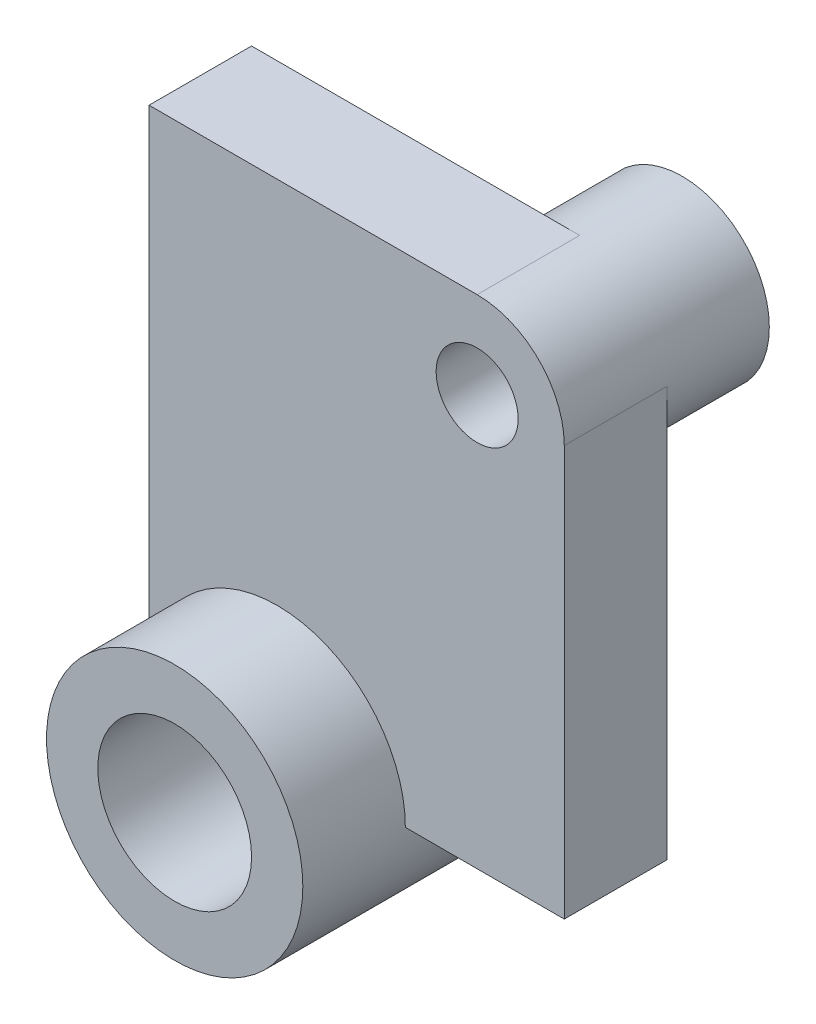
SolidWorks part; units mm, degrees
ref_plane "Спереди" through (0, 0, 0) normal (0, 0, 1) x (1, 0, 0)
ref_plane "Сверху" through (0, 0, 0) normal (0, 1, 0) x (1, 0, 0)
ref_plane "Справа" through (0, 0, 0) normal (1, 0, 0) x (0, 0, -1)
sketch "Эскиз1" plane through (0, 0, 0) normal (0, 0, 1) x (1, 0, 0)
  line L0 (0, 0) -> (0, -40) construction
  line L1 (13, -40) -> (13, -15)
  line L2 (13, -15) -> (8.1885, 2.28)
  line L3 (-13, -40) -> (-32, -40)
  line L4 (-32, -40) -> (-32, -15)
  line L5 (-32, -15) -> (-5.3529, 6.6028)
  line L6 (-13, -40) -> (-8.5, -40)
  line L7 (13, -40) -> (8.5, -40)
  circle A0 centre (0, 0) radius 5.5
  circle A1 centre (0, -40) radius 13
  circle A2 centre (0, 0) radius 8.5
  circle A3 centre (0, -40) radius 8.5
  circle A4 centre (0, 0) radius 4
  dimension "D1" = 11
  dimension "D2" = 26
  dimension "D7" = 17
  dimension "D8" = 8
  dimension "D3" = 40
  dimension "D5" = 45
  dimension "D6" = 25
  dimension "D4" = 3
extrude "Бобышка-Вытянуть1" add sketch "Эскиз1" along normal blind 10 contours A2 L0 A1 L1 L2 | L0 A2 L5 L4 L3 A1 | A1 A3 | A0 A2 | A0 | L0 A1 L6 A3 | A1 L0 A3 L7 | A3 region at (-3.7791, 3.7791, 0) region at (-7.7851, -2.7593, 0) region at (6.9511, -18.2389, 0) region at (-16.6766, -20.8491, 0) region at (6.9436, -33.0564, 0) region at (-6.9436, -33.0564, 0) region at (5.8404, -34.1596, 0) region at (0, -52.7093, 0)
sketch "Эскиз2" plane through (0, 0, 10) normal (0, 0, 1) x (1, 0, 0)
  line L0 (-13, -40) -> (13, -40)
  arc A0 (-13, -40) -> (13, -40) centre (0, -40) ccw construction
  arc A1 (-13, -40) -> (13, -40) centre (0, -40) ccw
extrude "Вырез-Вытянуть1" cut sketch "Эскиз2" against normal through all
sketch "Эскиз3" plane through (0, 0, 10) normal (0, 0, 1) x (1, 0, 0)
  line L0 (13, -40) -> (-32, -40) construction
  line L1 (-32, -40) -> (-32, -15) construction
  circle A0 centre (-19.5, -40) radius 12.5
  dimension "D1" = 25
extrude "Бобышка-Вытянуть2" add sketch "Эскиз3" against normal up to surface (10 mm away) contours A0 up to face at (-5.6662, -16.2435, 0)
sketch "Эскиз4" plane through (0, 0, 10) normal (0, 0, 1) x (1, 0, 0)
  circle A0 centre (-19.5, -40) radius 7.5
  dimension "D1" = 15
extrude "Вырез-Вытянуть2" cut sketch "Эскиз4" against normal up to next
sketch "Эскиз5" plane through (0, 0, 10) normal (0, 0, 1) x (1, 0, 0)
  circle A0 centre (-19.5, -40) radius 7.5
  circle A1 centre (-19.5, -40) radius 12.5
  circle A3 centre (-19.5, -40) radius 7.5 construction
extrude "Бобышка-Вытянуть3" add sketch "Эскиз5" along normal blind 10
sketch "Эскиз6" plane through (0, 0, 0) normal (0, 0, -1) x (-1, 0, 0)
  circle A0 centre (0, 0) radius 4 construction
  circle A1 centre (0, 0) radius 4
  circle A2 centre (0, 0) radius 8.5
extrude "Бобышка-Вытянуть4" add sketch "Эскиз6" along normal blind 10
sketch "Эскиз7" plane through (0, 0, 10) normal (0, 0, 1) x (1, 0, 0)
  line L0 (-32, -15) -> (-32, 8.5)
  line L1 (-32, 8.5) -> (13, 8.5)
  line L2 (13, 8.5) -> (13, -15)
  line L3 (13, -40) -> (13, -15) construction
  line L4 (-32, -15) -> (-5.3529, 6.6028) construction
  line L5 (13, -15) -> (8.1885, 2.28) construction
  line L6 (-32, -15) -> (-5.3529, 6.6028)
  line L7 (13, -15) -> (8.1885, 2.28)
  arc A0 (8.1885, 2.28) -> (-5.3529, 6.6028) centre (0, 0) ccw construction
  arc A1 (8.1885, 2.28) -> (-5.3529, 6.6028) centre (0, 0) ccw
  line M4 (13, -15) -> (8.1885, 2.28)
  arc M5 (8.1885, 2.28) -> (-5.3529, 6.6028) centre (0, 0) ccw
  line M6 (-5.3529, 6.6028) -> (-32, -15)
extrude "Бобышка-Вытянуть5" add sketch "Эскиз7" against normal up to surface (10 mm away) contours L1 L0 M6 M5 | L2 L1 M5 M4 region at (10.3149, 1.2749, 10) region at (-22.2807, 0.6884, 10) up to face at (-12, -40, 0)
sketch "Эскиз8" plane through (0, 0, 0) normal (0, 0, -1) x (-1, 0, 0)
  line L0 (-8.5, 0) -> (-8.5, -40)
  line L1 (-13, -40) -> (7, -40) construction
  line L2 (-8.5, -40) -> (-13, -40)
  line L3 (-13, -40) -> (-13, 8.5)
  line L4 (-13, 8.5) -> (0, 8.5)
  circle A0 centre (0, 0) radius 8.5 construction
  circle A1 centre (0, 0) radius 8.5
  circle M2 centre (0, 0) radius 8.5
  line M3 (0, 8.5) -> (-13, 8.5)
  line M4 (-13, 8.5) -> (-13, -40)
  line M5 (-13, -40) -> (7, -40)
extrude "Вырез-Вытянуть3" cut sketch "Эскиз8" against normal through all contours L0 M2 M3 M4 M5 region at (10.4748, -14.2674, 0)
